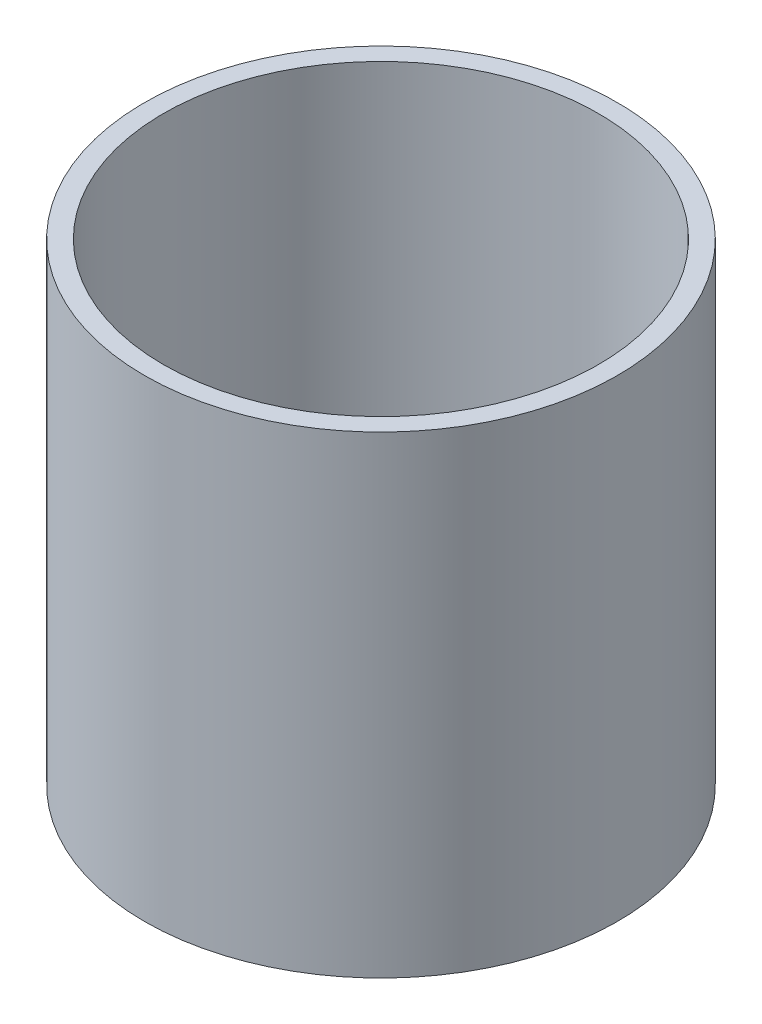
SolidWorks part; units mm, degrees
material "7075-T6 (SN)"
ref_plane "Front Plane" through (0, 0, 0) normal (0, 0, 1) x (1, 0, 0)
ref_plane "Top Plane" through (0, 0, 0) normal (0, 1, 0) x (1, 0, 0)
ref_plane "Right Plane" through (0, 0, 0) normal (1, 0, 0) x (0, 0, -1)
sketch "Sketch1" plane through (0, 0, 0) normal (0, 1, 0) x (1, 0, 0)
  circle A0 centre (0, 0) radius 1250
  circle A1 centre (0, 0) radius 1150
  circle A2 centre (0, 0) radius 1200 construction
  dimension "D1" = 2300
  dimension "D2" = 2500
  dimension "D3" = 2400
extrude "Boss-Extrude1" add sketch "Sketch1" along normal blind 2500
